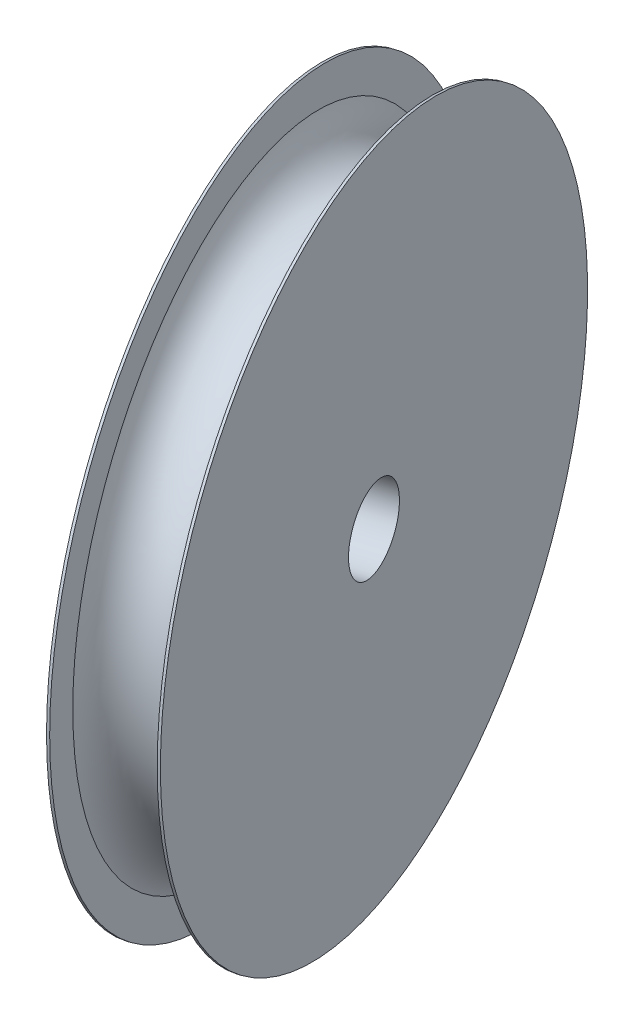
SolidWorks part; units mm, degrees
material "Default"
ref_plane "Top" through (0, 0, 0) normal (0, 0, 1) x (1, 0, 0)
ref_plane "Right" through (0, 0, 0) normal (0, 1, 0) x (1, 0, 0)
ref_plane "Front" through (0, 0, 0) normal (1, 0, 0) x (0, 0, -1)
ref_axis "Axis1" through (-81.5738, -109.2383, 112.1532) along (0.9527, 0, -0.3041)
ref_plane "Plane1" through (24.9448, 0, 78.1561) normal (-0.3041, 0, -0.9527) x (-0.9527, 0, 0.3041)
sketch "Sketch1" plane through (24.9448, 0, 78.1561) normal (-0.3041, 0, -0.9527) x (-0.9527, 0, 0.3041)
  line L0 (113.1991, -107.8883) -> (98.1991, -107.8883) construction
  line L1 (105.6991, -107.8883) -> (105.6991, -104.9713) construction
  line L2 (107.6041, -107.5883) -> (103.7941, -107.5883)
  line L3 (103.7941, -107.5883) -> (103.7941, -95.3883)
  line L4 (107.6041, -95.3883) -> (103.7941, -95.3883) construction
  line L5 (107.6041, -107.5883) -> (107.6041, -95.3883)
  line L6 (101.5029, -107.8883) -> (101.5029, -95.3883) construction
  line L7 (101.5029, -95.3883) -> (101.5029, -91.2883) construction
  line L8 (101.5029, -91.2883) -> (105.1029, -91.2883) construction
  line L9 (103.8991, -96.8883) -> (107.4991, -96.8883) construction
  line L10 (105.6991, -95.3883) -> (105.6991, -92.7384) construction
  line L11 (103.8991, -96.8883) -> (103.8991, -95.3883)
  line L12 (107.4991, -96.8883) -> (107.4991, -95.3883)
  line L13 (103.7941, -95.3883) -> (103.8991, -95.3883)
  line L14 (107.4991, -95.3883) -> (107.6041, -95.3883)
  arc A0 (103.8991, -96.8883) -> (107.4991, -96.8883) centre (105.6991, -96.3092) ccw
  point P11 (105.6991, -107.5883)
  point P12 (105.6991, -95.3883)
  point P19 (105.6991, -96.8883)
  dimension "D1" = 1.905
  dimension "D2" = 0.3
  dimension "D3" = 3.6
  dimension "D4" = 12.5
  dimension "D5" = 4.1
  dimension "D6" = 3.6
  dimension "D7" = 1.5
revolve "Revolve1" add sketch "Sketch1" angle 360 about axis through (-81.5738, -109.2383, 112.1532) along (0.9527, 0, -0.3041)
fillet "Fillet1" radius 1.524 rebuild error yes
